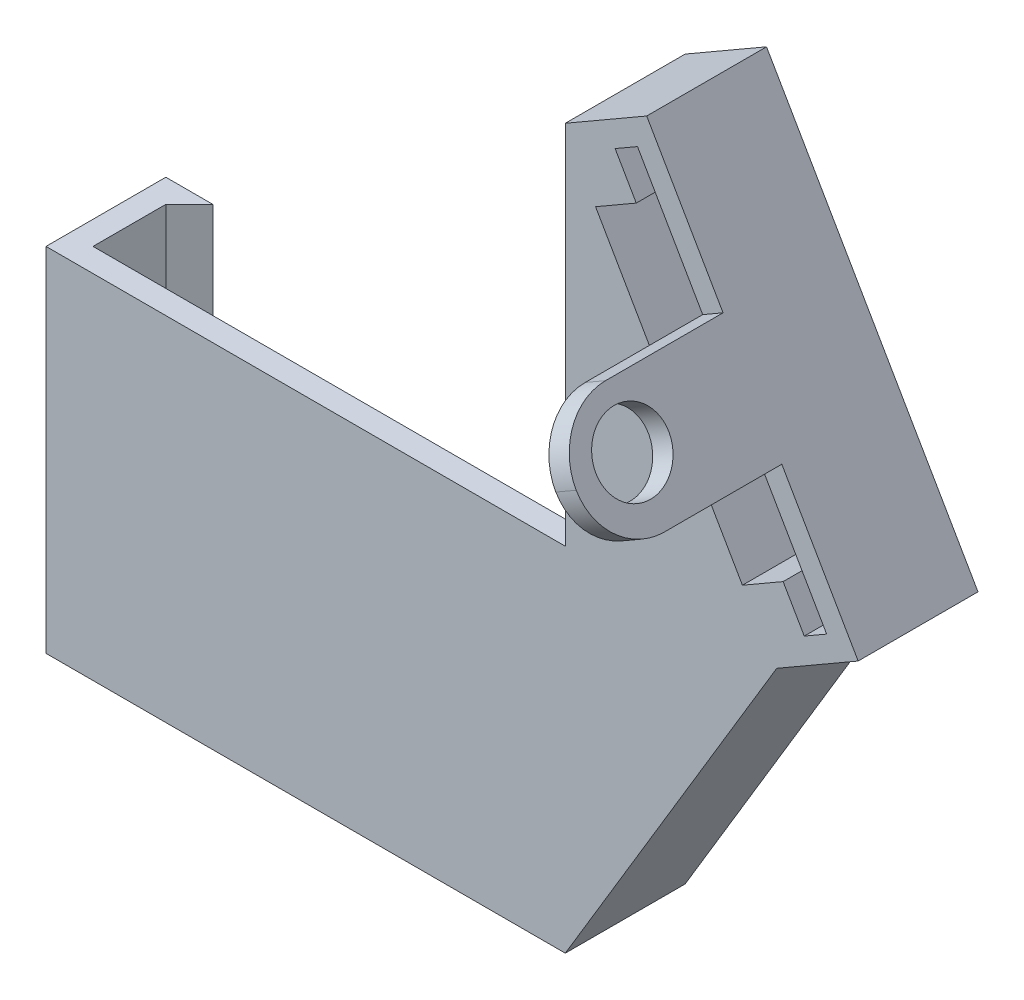
SolidWorks part; units mm, degrees
ref_plane "Front Plane" through (0, 0, 0) normal (0, 0, 1) x (1, 0, 0)
ref_plane "Top Plane" through (0, 0, 0) normal (0, 1, 0) x (1, 0, 0)
ref_plane "Right Plane" through (0, 0, 0) normal (1, 0, 0) x (0, 0, -1)
sketch "Sketch1" plane through (0, 0, 0) normal (0, 1, 0) x (1, 0, 0)
  line L0 (18.1, 3.1) -> (18.1, 5.1)
  line L1 (20.1, -3.1) -> (-20.1, -3.1)
  line L2 (20.1, -3.1) -> (20.1, 3.1)
  line L3 (20.1, 3.1) -> (18.1, 3.1)
  line L4 (-20.1, -3.1) -> (-20.1, 3.1)
  line L5 (20.1, -3.1) -> (-20.1, 3.1) construction
  line L6 (20.1, 3.1) -> (-20.1, -3.1) construction
  line L7 (18.1, 5.1) -> (22.1, 5.1)
  line L8 (22.1, 5.1) -> (22.1, -5.1)
  line L9 (22.1, -5.1) -> (-22.1, -5.1)
  line L10 (-22.1, -5.1) -> (-22.1, 5.1)
  line L11 (-22.1, 5.1) -> (-18.1, 5.1)
  line L12 (-18.1, 5.1) -> (-20.1, 3.1)
  point P0 (0, 0)
  dimension "D1" = 40.2
  dimension "D2" = 6.2
  dimension "D3" = 2
  dimension "D4" = 2
  dimension "D5" = 45
  dimension "D6" = 2
  dimension "D7" = 2
  dimension "D8" = 2
extrude "Boss-Extrude1" add sketch "Sketch1" along normal blind 30
sketch "Sketch2" plane through (0, 0, 5.1) normal (0, 0, 1) x (1, 0, 0)
  line L0 (47.0282, 34) -> (29.0282, 65.1769)
  line L5 (47.0282, 34) -> (40.1, 30)
  line L6 (29.0282, 65.1769) -> (22.1, 61.1769)
  line L8 (47.0282, 34) -> (22.1, 61.1769) construction
  line L9 (29.0282, 65.1769) -> (40.1, 30) construction
  line L11 (40.1, 30) -> (22.1, 0)
  line L12 (22.1, 0) -> (22.1, 30)
  line L13 (40.1, 30) -> (22.1, 30) construction
  line L14 (22.1, 30) -> (22.1, 61.1769)
  point P1 (34.5641, 47.5885)
  dimension "D1" = 30
  dimension "D2" = 36
  dimension "D3" = 8
extrude "Boss-Extrude2" add sketch "Sketch2" against normal up to surface (10.2 mm away) up to face at (20.1, 15, -5.1)
sketch "Sketch3" plane through (0, 0, 5.1) normal (0, 0, 1) x (1, 0, 0)
  line L0 (44.3462, 34.6454) -> (28.2462, 62.5315)
  line L1 (44.3462, 34.6454) -> (42.4409, 33.5454)
  line L2 (28.2462, 62.5315) -> (26.3409, 61.4315)
  line L3 (42.4409, 33.5454) -> (40.6409, 36.6631)
  line L4 (44.3462, 34.6454) -> (26.3409, 61.4315) construction
  line L5 (28.2462, 62.5315) -> (42.4409, 33.5454) construction
  line L6 (47.0282, 34) -> (29.0282, 65.1769) construction
  line L7 (35.3435, 48.0385) -> (38.0282, 49.5885) construction
  line L9 (28.1409, 58.3138) -> (24.6768, 56.3138)
  line L10 (40.6409, 36.6631) -> (37.1768, 34.6631)
  line L11 (24.6768, 56.3138) -> (37.1768, 34.6631)
  line L12 (28.1409, 58.3138) -> (26.3409, 61.4315)
  line L13 (35.3435, 48.0385) -> (30.9268, 45.4885) construction
  point P1 (35.3435, 48.0385)
  dimension "D1" = 2
  dimension "D2" = 2.2
  dimension "D3" = 32.2
  dimension "D4" = 25
  dimension "D5" = 4
extrude "Cut-Extrude1" cut sketch "Sketch3" against normal up to surface (10.2 mm away) up to face at (27.3321, 31.2942, -5.1)
mirror "Mirror1" [suppressed] about plane through (0, 0, 0) normal (0, 1, 0) of bodies 103
delete or keep bodies "Body-Delete/Keep 1" [suppressed] type delete bodies bodies 103
sketch "Sketch4" plane through (49.9936, 28.8638, 0) normal (0.866, 0.5, 0) x (0, 0, -1)
  line L0 (-5.1, 5.9308) -> (-5.1, 41.9308) construction
  line L1 (-5.1, 18.9308) -> (-20.1, 18.9308)
  line L2 (-5.1, 18.9308) -> (-5.1, 28.9308)
  line L3 (-5.1, 28.9308) -> (-20.1, 28.9308)
  line L4 (-20.1, 18.9308) -> (-20.1, 28.9308)
  point P6 (-5.1, 23.9308)
  point P7 (-5.1, 23.9308)
  dimension "D1" = 10
  dimension "D2" = 15
extrude "Boss-Extrude3" add sketch "Sketch4" against normal up to surface (2 mm away) up to face at (36.2962, 48.5885, 0)
fillet "Fillet1" radius 5 2 edges at (34.6622, 53.4186, 20.1) (39.6622, 44.7583, 20.1)
sketch "Sketch5" plane through (49.9936, 28.8638, 0) normal (0.866, 0.5, 0) x (0, 0, -1)
  circle A0 centre (-15.1753, 24.2256) radius 3.1
  dimension "D1" = 6.2
extrude "Cut-Extrude2" cut sketch "Sketch5" against normal up to next
